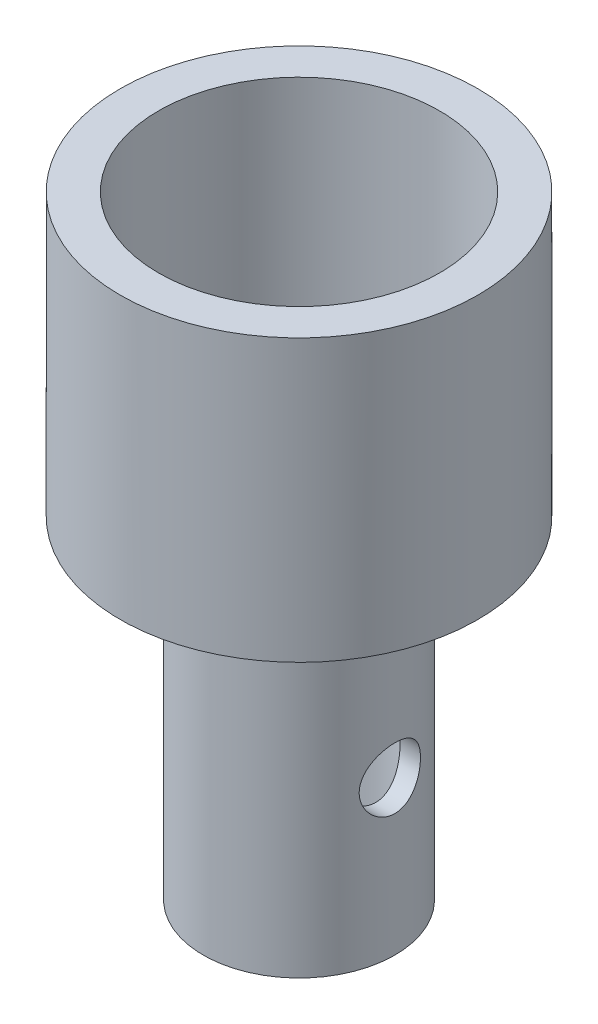
SolidWorks part; units mm, degrees
note: '?' marks a value the reader was unsure of.
ref_plane "Front Plane" through (0, 0, 0) normal (0, 0, 1) x (1, 0, 0)
ref_plane "Top Plane" through (0, 0, 0) normal (0, 1, 0) x (1, 0, 0)
ref_plane "Right Plane" through (0, 0, 0) normal (1, 0, 0) x (0, 0, -1)
sketch "Sketch1" plane through (0, 0, 0) normal (0, 1, 0) x (1, 0, 0)
  circle A0 centre (0, 0) radius 17.4625
  circle A1 centre (0, 0) radius 22.225
  dimension "D1" = 34.925
  dimension "D2" = 4.7625
extrude "spring_chamber" add sketch "Sketch1" along normal blind 28.575 contours A1 A0
sketch "Sketch2" plane through (0, 0, 0) normal (0, -1, 0) x (1, 0, 0)
  circle A0 centre (0, 0) radius 9.525
  circle A1 centre (0, 0) radius 22.225 construction
  circle A2 centre (0, 0) radius 22.225
  dimension "D1" = 19.05
extrude "ball_chamber" add sketch "Sketch2" along normal blind 47.625
ref_axis "Axis1" through (0, 28.575, 0) along (0, -1, 0)?
sketch "Sketch3" plane through (0, -47.625, 0) normal (0, -1, 0) x (1, 0, 0)
  circle A0 centre (0, 0) radius 22.225 construction
  circle A1 centre (0, 0) radius 22.225
sketch "Sketch5" plane through (0, 0, 0) normal (1, 0, 0) x (0, 0, -1)
  line L0 (17.4625, 0) -> (-17.4625, 0) construction
  line L1 (-22.225, -47.625) -> (22.225, -47.625) construction
  line L2 (-22.225, -47.625) -> (22.225, -47.625)
  line L4 (17.4625, 0) -> (-17.4625, 0)
  circle A0 centre (0, -28.575) radius 3.81
  point P4 (0, 0)
  dimension "D1" = 7.62
  dimension "D2" = 28.575
extrude "ball_hole" cut sketch "Sketch5" along normal through all contours A0
sketch "Sketch8" plane through (0, -47.625, 0) normal (0, -1, 0) x (1, 0, 0)
  circle A0 centre (0, 0) radius 11.9062
  circle A5 centre (0, 0) radius 9.525 construction
  circle A6 centre (0, 0) radius 9.525
  dimension "D1" = 2.3812
extrude "Cut-Extrude2" cut sketch "Sketch8" against normal offset from surface (41.275 mm away) 6.35
mirror "Mirror1" about plane through (0, 0, 0) normal (1, 0, 0) of "ball_hole"
